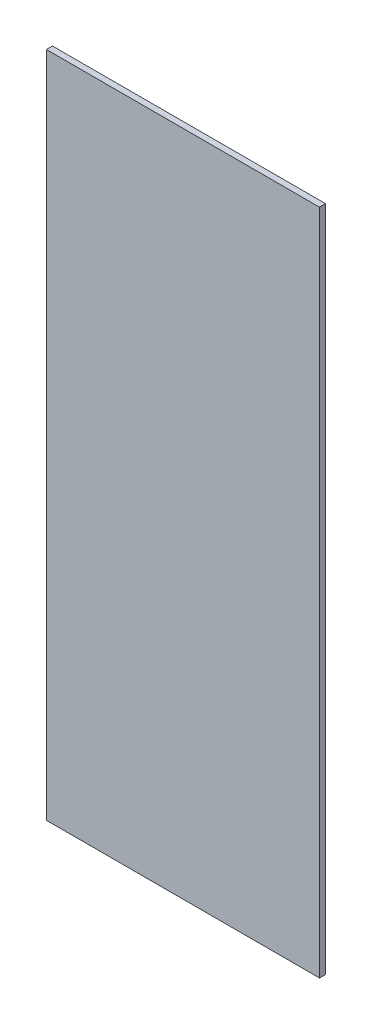
SolidWorks part; units mm, degrees
material "201 Annealed Stainless Steel (SS)"
ref_plane "Front Plane" through (0, 0, 0) normal (0, 0, 1) x (1, 0, 0)
ref_plane "Top Plane" through (0, 0, 0) normal (0, 1, 0) x (1, 0, 0)
ref_plane "Right Plane" through (0, 0, 0) normal (1, 0, 0) x (0, 0, -1)
sketch "Sketch1" plane through (0, 0, 0) normal (0, 0, 1) x (1, 0, 0)
  line L1 (-45, -110) -> (45, -110)
  line L2 (-45, -110) -> (-45, 110)
  line L3 (-45, 110) -> (45, 110)
  line L4 (45, -110) -> (45, 110)
  line L5 (-45, -110) -> (45, 110) construction
  line L6 (-45, 110) -> (45, -110) construction
  point P0 (0, 0)
  dimension "D1" = 90
  dimension "D2" = 220
extrude "Boss-Extrude1" add sketch "Sketch1" along normal blind 2
sketch "Sketch2" plane through (0, 0, 0) normal (0, 0, -1) x (-1, 0, 0)
  line L0 (61, 145) -> (61, -145) construction
  line L1 (-61, 314.7216) -> (-204.3993, 314.7216)
  line L2 (-61, 314.7216) -> (-61, -251.9618)
  line L3 (-61, -251.9618) -> (-204.3993, -251.9618)
  line L4 (-204.3993, 314.7216) -> (-204.3993, -251.9618)
  line L6 (61, 279.3211) -> (244.4765, 279.3211)
  line L7 (61, 279.3211) -> (61, -295.1839)
  line L8 (61, -295.1839) -> (244.4765, -295.1839)
  line L9 (244.4765, 279.3211) -> (244.4765, -295.1839)
  line L10 (-61, -145) -> (-61, 145) construction
  dimension "D1" = 122
extrude "Cut-Extrude1" [suppressed] cut sketch "Sketch2" against normal through all
sketch "Sketch3" [suppressed] plane through (49, 0, 0) normal (1, 0, 0) x (0, 0, -1)
  circle A0 centre (-6.722, 55.3681) radius 5.3835
surface "Surface-Extrude1" [suppressed] sketch "Sketch3"
sketch "Sketch4" [suppressed] plane through (-49, 0, 0) normal (-1, 0, 0) x (0, 0, 1)
  line L1 (2, 80) -> (0, 80) construction
  line L2 (0, -80) -> (0, 80) construction
  point P0 (7.5, 76)
  dimension "D1" = 4
  dimension "D2" = 7.5
ref_axis "Axis1" [suppressed] through (-49, 76, 7.5) along (1, 0, 0)
sketch "Sketch5" [suppressed] plane through (0, 0, 0) normal (0, 0, -1) x (-1, 0, 0)
  line L0 (49, 80) -> (49, -80) construction
  line L1 (-49, 80) -> (49, 80)
  line L2 (-49, 80) -> (-49, 60.2594)
  line L3 (-49, 60.2594) -> (49, 60.2594)
  line L4 (49, 80) -> (49, 60.2594)
extrude "Cut-Extrude2" [suppressed] cut sketch "Sketch5" against normal blind 3
sketch "Sketch6" [suppressed] plane through (0, 0, 2) normal (0, 0, 1) x (1, 0, 0)
  line L0 (0, 0) -> (103.2002, 0) construction
  line L1 (-40, 80) -> (-40, 108.3319) construction
  line L2 (-40, 80) -> (-27.987, 80) construction
  line L3 (0, 0) -> (0, 138.3235) construction
  line L4 (40, 80) -> (27.987, 80) construction
  line L5 (40, 80) -> (40, 108.3319) construction
  line L6 (40, -80) -> (40, -108.3319) construction
  line L7 (40, -80) -> (27.987, -80) construction
  line L8 (-40, -80) -> (-27.987, -80) construction
  line L9 (-40, -80) -> (-40, -108.3319) construction
  circle A0 centre (-40, 80) radius 4.5
  circle A2 centre (-45.8, 85.8) radius 1.95
  circle A3 centre (-45.8, 74.2) radius 1.95
  circle A4 centre (-34.2, 74.2) radius 1.95
  circle A5 centre (-34.2, 85.8) radius 1.95
  circle A6 centre (34.2, 85.8) radius 1.95
  circle A7 centre (34.2, 74.2) radius 1.95
  circle A8 centre (45.8, 74.2) radius 1.95
  circle A9 centre (45.8, 85.8) radius 1.95
  circle A10 centre (40, 80) radius 4.5
  circle A11 centre (40, -80) radius 4.5
  circle A12 centre (45.8, -85.8) radius 1.95
  circle A13 centre (45.8, -74.2) radius 1.95
  circle A14 centre (34.2, -74.2) radius 1.95
  circle A15 centre (34.2, -85.8) radius 1.95
  circle A16 centre (-34.2, -85.8) radius 1.95
  circle A17 centre (-34.2, -74.2) radius 1.95
  circle A18 centre (-45.8, -74.2) radius 1.95
  circle A19 centre (-45.8, -85.8) radius 1.95
  circle A20 centre (-40, -80) radius 4.5
  circle A21 centre (-40, 80) radius 5.1 construction
  dimension "D1" = 9
  dimension "D3" = 3.9
extrude "Leandut_holes" [suppressed] cut sketch "Sketch6" against normal through all
chamfer "Chamfer1" [suppressed] distance 5 angle 45
sketch "Sketch7" [suppressed] plane through (0, 0, 2) normal (0, 0, 1) x (1, 0, 0)
  line L0 (106, 145) -> (-106, 145) construction
  line L1 (-56, -95) -> (56, -95)
  line L2 (-56, -95) -> (-56, 125)
  line L3 (-56, 125) -> (56, 125)
  line L4 (56, -95) -> (56, 125)
  line L5 (0, 0) -> (0, -66.8576) construction
  line L7 (-106, 145) -> (-106, -145) construction
  point P0 (0, 0)
  dimension "D1" = 20
  dimension "D2" = 50
  dimension "D3" = 112
  dimension "D4" = 125
extrude "Plunger-Window" [suppressed] cut sketch "Sketch7" against normal through all
sketch "Sketch8" [suppressed] plane through (0, 0, 2) normal (0, 0, 1) x (1, 0, 0)
  line L0 (106, 145) -> (56, 145) construction
  line L1 (-56, 125) -> (56, 125)
  line L2 (-56, 125) -> (-56, 145)
  line L3 (-56, 145) -> (56, 145)
  line L4 (56, 125) -> (56, 145)
  line L5 (56, -95) -> (56, 125) construction
extrude "Cut-Extrude3" [suppressed] cut sketch "Sketch8" against normal blind 5
